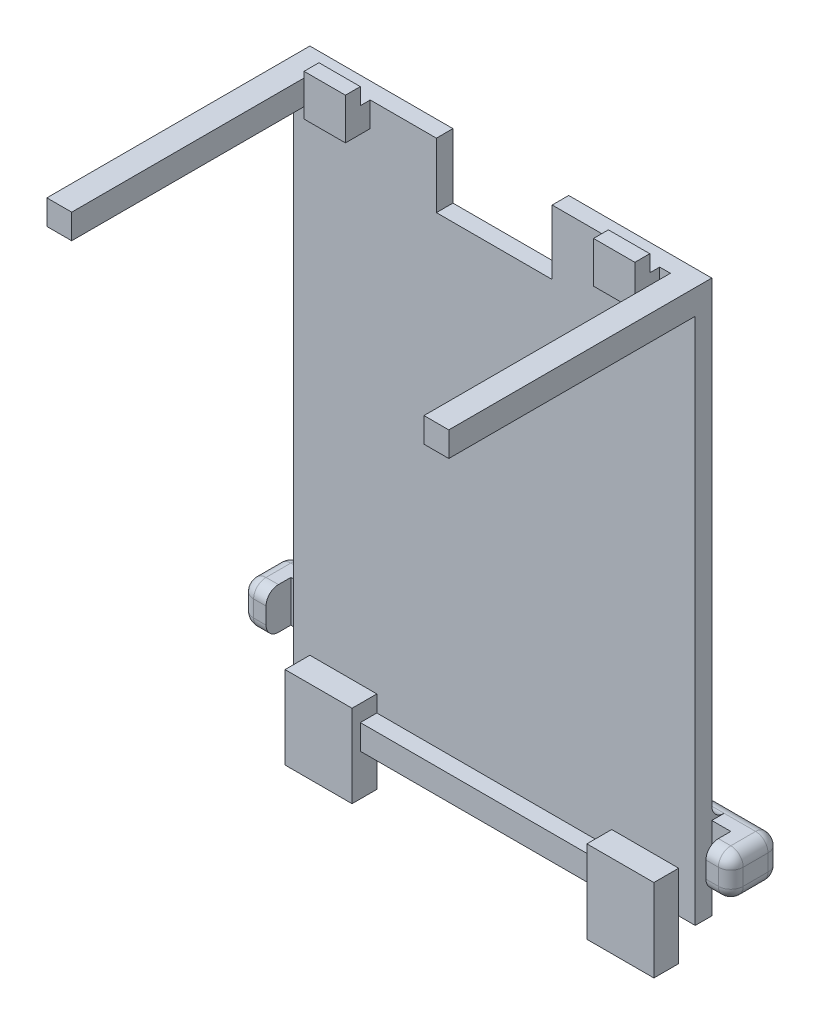
SolidWorks part; units mm, degrees
ref_plane "前视基准面" through (0, 0, 0) normal (0, 0, 1) x (1, 0, 0)
ref_plane "上视基准面" through (0, 0, 0) normal (0, 1, 0) x (1, 0, 0)
ref_plane "右视基准面" through (0, 0, 0) normal (1, 0, 0) x (0, 0, -1)
other "Configuration Table"
sketch "草图1" plane through (0, 0, -32) normal (0, 0, -1) x (-1, 0, 0)
  line L0 (-41, 12) -> (12, 12) construction
  line L1 (-38.8, 78.8) -> (9.8, 78.8)
  line L2 (-38.8, 78.8) -> (-38.8, 12)
  line L3 (-38.8, 12) -> (9.8, 12)
  line L4 (9.8, 78.8) -> (9.8, 12)
  line L5 (-39, 12) -> (-39, 82) construction
  line L6 (10, 79) -> (10, 12) construction
  line L10 (-39, 79) -> (-23, 79) construction
  dimension "D1" = 0.2
  dimension "D2" = 0.2
  dimension "D3" = 0.2
extrude "凸台-拉伸1" add sketch "草图1" against normal up to surface (2 mm away)
sketch "草图2" plane through (0, 0, -30) normal (0, 0, 1) x (1, 0, 0)
  line L0 (-8, 17) -> (-8, 12) construction
  line L1 (-7.8, 17) -> (0.3, 17)
  line L2 (-7.8, 17) -> (-7.8, 7)
  line L3 (-7.8, 7) -> (0.3, 7)
  line L4 (0.3, 17) -> (0.3, 7)
  line L5 (38.8, 12) -> (-9.8, 12) construction
  line L6 (0.5, 12) -> (0.5, 6) construction
  dimension "D1" = 0.2
  dimension "D2" = 10
  dimension "D3" = 5
  dimension "D4" = 0.2
extrude "凸台-拉伸2" add sketch "草图2" along normal blind 3
ref_plane "基准面1" through (14.5, 0, 0) normal (-1, 0, 0) x (0, 0, 1)
mirror "镜向1" about plane through (14.5, 0, 0) normal (-1, 0, 0) of "凸台-拉伸2"
sketch "草图3" plane through (0, 0, -30) normal (0, 0, 1) x (1, 0, 0)
  line L0 (-12, 12) -> (41, 12) construction
  line L1 (0.3, 15) -> (28.7, 15)
  line L2 (0.3, 15) -> (0.3, 12)
  line L3 (0.3, 12) -> (28.7, 12)
  line L4 (28.7, 15) -> (28.7, 12)
  line L6 (0.3, 12) -> (0.3, 17) construction
  line L7 (28.7, 12) -> (28.7, 17) construction
  dimension "D1" = 3
extrude "凸台-拉伸3" add sketch "草图3" along normal blind 2
sketch "草图4" plane through (0, 0, -32) normal (0, 0, -1) x (-1, 0, 0)
  line L0 (-14.5, 78.8) -> (-14.5, 33.7688) construction
  line L1 (9.8, 78.8) -> (-38.8, 78.8) construction
  line L3 (-21.5, 79) -> (-7.5, 79)
  line L4 (-21.5, 79) -> (-21.5, 71)
  line L5 (-21.5, 71) -> (-7.5, 71)
  line L6 (-7.5, 79) -> (-7.5, 71)
  line L7 (-39, 79) -> (-23, 79) construction
  dimension "D1" = 8
extrude "切除-拉伸1" cut sketch "草图4" against normal through all
sketch "草图5" plane through (0, 0, -30) normal (0, 0, 1) x (1, 0, 0)
  line L0 (14.5, 71) -> (14.5, 35.8876) construction
  line L1 (7.5, 71) -> (21.5, 71) construction
  line L2 (-9.8, 78.8) -> (7.5, 78.8) construction
  line L3 (-5.5, 80.8) -> (-0.5, 80.8)
  line L4 (-5.5, 80.8) -> (-5.5, 75.8)
  line L5 (-5.5, 75.8) -> (-0.5, 75.8)
  line L6 (-0.5, 80.8) -> (-0.5, 75.8)
  line L7 (29.5, 80.8) -> (29.5, 75.8)
  line L8 (34.5, 75.8) -> (29.5, 75.8)
  line L9 (34.5, 80.8) -> (34.5, 75.8)
  line L10 (34.5, 80.8) -> (29.5, 80.8)
  dimension "D1" = 2
  dimension "D2" = 5
  dimension "D3" = 5
  dimension "D4" = 15
extrude "凸台-拉伸4" add sketch "草图5" along normal blind 3
sketch "草图6" plane through (0, 80.8, 0) normal (0, 1, 0) x (1, 0, 0)
  line L0 (-0.5, 30) -> (-5.5, 30) construction
  line L1 (-5.5, 30) -> (-0.5, 30)
  line L2 (-5.5, 30) -> (-5.5, 28.8)
  line L3 (-5.5, 28.8) -> (-0.5, 28.8)
  line L4 (-0.5, 30) -> (-0.5, 28.8)
  line L6 (-5.5, 27) -> (-5.5, 30) construction
  line L7 (-0.5, 27) -> (-0.5, 30) construction
  line L8 (14.5, 32) -> (14.5, 4.8493) construction
  line L10 (29.5, 30) -> (29.5, 28.8)
  line L11 (34.5, 28.8) -> (29.5, 28.8)
  line L12 (34.5, 30) -> (34.5, 28.8)
  line L13 (34.5, 30) -> (29.5, 30)
  line L14 (-10, 29) -> (39, 29) construction
  line L15 (41, 32) -> (-12, 32) construction
  dimension "D1" = 0.2
extrude "切除-拉伸2" cut sketch "草图6" against normal up to surface (2 mm away) up to face at (-1.7667, 78.8, -30.6667)
sketch "草图7" plane through (0, 0, -30) normal (0, 0, 1) x (1, 0, 0)
  line L0 (14.5, 71) -> (14.5, 61.8228) construction
  line L1 (-9.8, 78.8) -> (-6.8, 78.8)
  line L2 (-9.8, 78.8) -> (-9.8, 75.8)
  line L3 (-9.8, 75.8) -> (-6.8, 75.8)
  line L4 (-6.8, 78.8) -> (-6.8, 75.8)
  line L5 (7.5, 71) -> (21.5, 71) construction
  line L6 (35.8, 78.8) -> (35.8, 75.8)
  line L7 (38.8, 75.8) -> (35.8, 75.8)
  line L8 (38.8, 78.8) -> (38.8, 75.8)
  line L9 (38.8, 78.8) -> (35.8, 78.8)
  dimension "D1" = 3
  dimension "D2" = 3
extrude "凸台-拉伸5" add sketch "草图7" along normal offset from surface (29.8 mm away) 0.2
sketch "草图8" plane through (0, 0, -32) normal (0, 0, -1) x (-1, 0, 0)
  line L1 (4.8, 22) -> (15.1, 22)
  line L2 (4.8, 22) -> (4.8, 17)
  line L3 (4.8, 17) -> (15.1, 17)
  line L4 (15.1, 22) -> (15.1, 17)
  line L5 (9.8, 12) -> (9.8, 78.8) construction
  line L6 (-41, 12) -> (12, 12) construction
  line L8 (12, 12) -> (12, 85) construction
  dimension "D1" = 5
  dimension "D2" = 5
  dimension "D3" = 3.1
  dimension "D4" = 5
extrude "凸台-拉伸6" add sketch "草图8" along normal blind 3
sketch "草图9" plane through (0, 0, -32) normal (0, 0, 1) x (1, 0, 0)
  line L0 (-15.1, 22) -> (-9.8, 22) construction
  line L1 (-15.1, 22) -> (-12.1, 22)
  line L2 (-15.1, 22) -> (-15.1, 17)
  line L3 (-15.1, 17) -> (-12.1, 17)
  line L4 (-12.1, 22) -> (-12.1, 17)
  line L5 (-15.1, 17) -> (-15.1, 22) construction
  line L7 (-9.8, 17) -> (-15.1, 17) construction
  line L8 (-12, 12) -> (-12, 85) construction
  dimension "D1" = 0.1
extrude "凸台-拉伸7" add sketch "草图9" along normal blind 3
fillet "圆角1" radius 1.5 12 edges at (-15.1, 19.5, -29) (-15.1, 22, -32) (-15.1, 17, -32) (-4.8, 19.5, -32) (-7.3, 17, -32) (-9.95, 17, -35) (-4.8, 19.5, -35) (-7.3, 22, -32) (-9.95, 22, -35) (-15.1, 19.5, -35) (-13.6, 22, -29) (-13.6, 17, -29)
ref_plane "基准面2" through (14.5, 0, 0) normal (-1, 0, 0) x (0, 0, 1)
mirror "镜向2" about plane through (14.5, 0, 0) normal (-1, 0, 0) of "圆角1", "凸台-拉伸7", "凸台-拉伸6"
